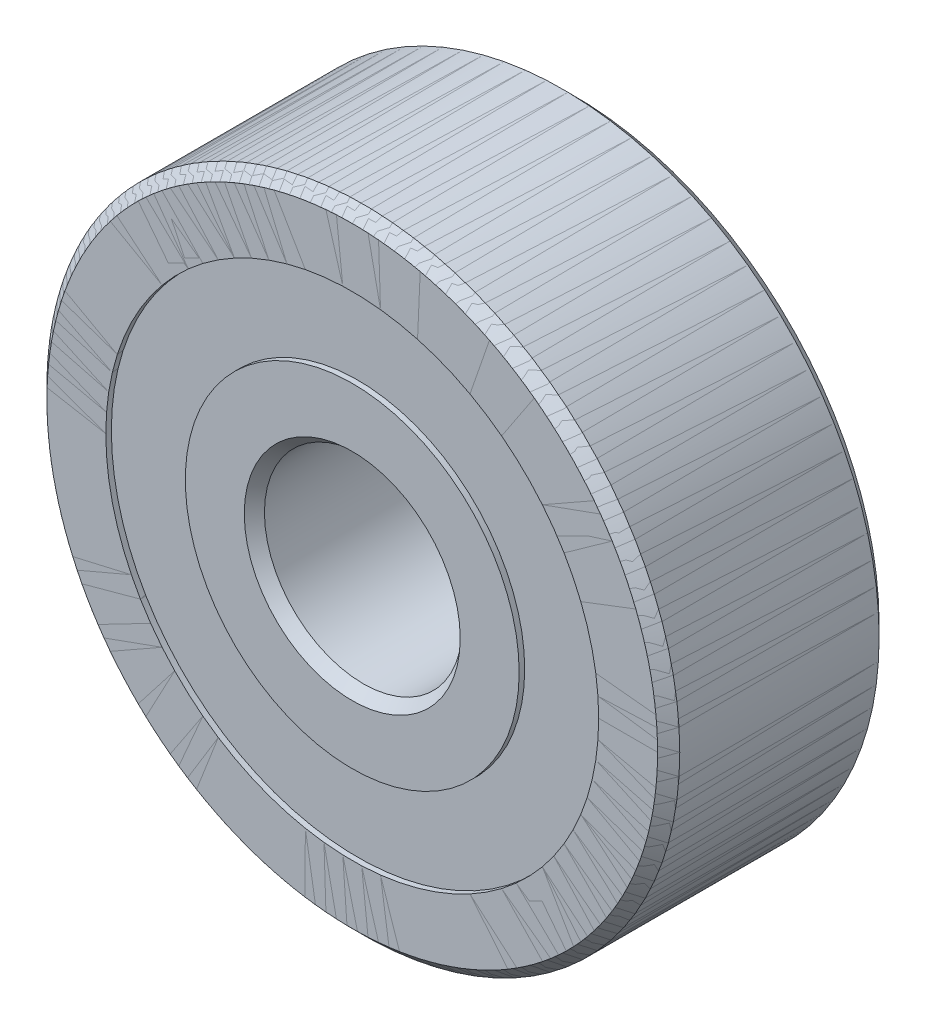
SolidWorks part; units mm, degrees
ref_plane "Front Plane" through (0, 0, 0) normal (0, 0, 1) x (1, 0, 0)
ref_plane "Top Plane" through (0, 0, 0) normal (0, 1, 0) x (1, 0, 0)
ref_plane "Right Plane" through (0, 0, 0) normal (1, 0, 0) x (0, 0, -1)
sketch "Sketch1" plane through (0, 0, 0) normal (1, 0, 0) x (0, 0, -1)
  line L0 (-1.4, 2.11) -> (1.4, 2.11) construction
  line L1 (-1.4, -2.11) -> (1.4, -2.11) construction
  line L2 (-1.4, 0) -> (1.4, 0) construction
  line L3 (0, 4) -> (0, -4) construction
  line L4 (0, 3.115) -> (0, 2.11) construction
  line L5 (1.4, 3.115) -> (-1.4, 3.115) construction
  line L7 (-1.4, -3.115) -> (1.4, -3.115) construction
  circle A0 centre (0, 2.6125) radius 0.625 construction
  circle A2 centre (0, -2.6125) radius 0.625 construction
  point P7 (0, 0)
  point P8 (0, -3.115)
  point P13 (0, -1.25)
  point P16 (0, -2.11)
  point P17 (-1.4, 0)
  point P18 (0, 1.25)
  point P19 (0, 3.115)
  point P29 (0, 2.11)
  dimension "Ball Dia" = 1.25
  dimension "ID" = 2.5
  dimension "Width" = 2.8
  dimension "OD" = 8
  dimension "Lo" = 6.23
  dimension "Li" = 4.22
sketch "Sketch8" plane through (0, 0, 0) normal (1, 0, 0) x (0, 0, -1)
  line L0 (-1.4, 0) -> (1.4, 0) construction
  line L2 (1.4, 4) -> (-1.4, 4)
  line L4 (-1.4, 4) -> (-1.4, 3.115)
  line L5 (-1.4, 3.115) -> (-0.3716, 3.115)
  line L6 (1.4, 3.115) -> (0.3716, 3.115)
  line L7 (1.4, 4) -> (1.4, 3.115)
  line L11 (1.4, 3.115) -> (-1.4, 3.115) construction
  circle A2 centre (0, 2.6125) radius 0.625 construction
  arc A3 (0.3716, 3.115) -> (-0.3716, 3.115) centre (0, 2.6125) ccw
revolve "Revolve1" add sketch "Sketch8" angle 360 about L0
chamfer "Chamfer1" distance 0.14 angle 45 2 edges at (4, 0, -1.4) (4, 0, 1.4)
sketch "Sketch2" plane through (0, 0, 0) normal (1, 0, 0) x (0, 0, -1)
  line L1 (1.26, 4) -> (1.26, -4) construction
  line L2 (0, 2.6125) -> (1.4, 2.6125) construction
  line L3 (-1.26, 4) -> (-1.26, -4) construction
  line L4 (-0.3716, 3.115) -> (-1.4, 3.115)
  line L6 (1.4, 2.11) -> (0.3716, 2.11)
  line L7 (-1.4, 1.365) -> (-1.4, 2.11)
  line L10 (1.4, 1.365) -> (1.4, 2.11)
  line L12 (1.26, 1.25) -> (-1.26, 1.25)
  line L13 (-1.26, 4) -> (-1.4, 3.86) construction
  line L14 (1.4, 3.86) -> (1.26, 4) construction
  line L15 (1.4, 4) -> (-1.4, 4) construction
  line L16 (1.4, 4) -> (1.4, 3.115) construction
  line L17 (-1.4, 4) -> (-1.4, 3.115) construction
  line L18 (1.4, 3.115) -> (-1.4, 3.115) construction
  line L19 (-1.26, 4) -> (-1.4, 3.86)
  line L20 (1.4, 3.86) -> (1.26, 4)
  line L21 (1.26, 4) -> (-1.26, 4)
  line L22 (1.4, 3.86) -> (1.4, 3.115)
  line L23 (-1.4, 3.86) -> (-1.4, 3.115)
  line L24 (1.4, 3.115) -> (0.3716, 3.115)
  line L25 (1.4, 1.365) -> (1.26, 1.25)
  line L26 (-1.26, 1.25) -> (-1.4, 1.365)
  line L27 (-0.3716, 2.11) -> (-1.4, 2.11)
  arc A0 (0.3716, 2.11) -> (-0.3716, 2.11) centre (0, 2.6125) cw
  circle A4 centre (0, 2.6125) radius 0.625 construction
  arc A5 (0.3716, 3.115) -> (-0.3716, 3.115) centre (0, 2.6125) ccw
revolve "Revolve2" add sketch "Sketch2" angle 360 about L0
sketch "Sketch3" plane through (0, 0, 0) normal (1, 0, 0) x (0, 0, -1)
  line L0 (-0.625, 2.6125) -> (0.625, 2.6125)
  line L1 (0, 2.6125) -> (0, 0) construction
  line L2 (0, 2.6125) -> (1.4, 2.6125) construction
  line L3 (-1.4, 0) -> (1.4, 0) construction
  circle A0 centre (0, 2.6125) radius 0.625 construction
  arc A2 (0.625, 2.6125) -> (-0.625, 2.6125) centre (0, 2.6125) ccw
  point P8 (0, 2.6125)
  dimension "D1" = 1.25
  dimension "D2" = 2.6125
revolve "Revolve3" add sketch "Sketch3" angle 360 about L0
ref_axis "Axis1" through (0, 0, -1.4) along (0, 0, 1)
pattern_circular "CirPattern1" count 7 every 51.429 about axis through (0, 0, -1.4) along (0, 0, 1) of bodies 104
sketch "Sketch5" plane through (0, 0, 0) normal (1, 0, 0) x (0, 0, -1)
  line L1 (1.4, 3.115) -> (-1.4, 3.115) construction
  line L2 (-1.4, 2.11) -> (1.4, 2.11) construction
  line L3 (-1.33, 3.115) -> (-0.625, 3.115)
  line L4 (-1.33, 3.115) -> (-1.33, 2.11)
  line L5 (-1.33, 2.11) -> (-0.625, 2.11)
  line L6 (-0.625, 3.115) -> (-0.625, 2.11)
  line L7 (0, 0) -> (0, 4) construction
  line L8 (0.625, 3.115) -> (0.625, 2.11)
  line L10 (-1.33, 3.93) -> (-1.33, 3.115) construction
  line L13 (1.33, 2.11) -> (0.625, 2.11)
  line L14 (1.33, 3.115) -> (1.33, 2.11)
  line L15 (1.33, 3.115) -> (0.625, 3.115)
  line L16 (-1.26, 4) -> (-1.4, 3.86) construction
  circle A1 centre (0, 2.6125) radius 0.625 construction
revolve "Revolve5" add sketch "Sketch5" angle 360 about L0
sketch "Sketch6" plane through (0, 0, 0) normal (0, 1, 0) x (1, 0, 0)
  line L0 (4, -1.26) -> (4, 1.26) construction
  point P0 (4, -1.4)
  point P1 (4, 1.4)
  dimension "D1" = 2.8
sketch "Sketch9" plane through (0, 0, 0) normal (0, 0, 1) x (1, 0, 0)
  line L0 (0, -4) -> (0, 4) construction
  line L3 (0, -1.25) -> (0, 1.25) construction
  point P7 (0, 0)
  point P11 (0, 0)
  dimension "D1" = 8
  dimension "D2" = 2.5
equation "\"D2@CirPattern1\" = 360/\"Balls@CirPattern1\""
equation "\"D1@Sketch6\" = \"Width@Sketch1\""
equation "\"D1@Sketch9\"=\"OD@Sketch1\""
equation "\"D2@Sketch9\" = \"ID@Sketch1\""
equation "\"D1@Chamfer1\"=\"Width@Sketch1\" * .05"
